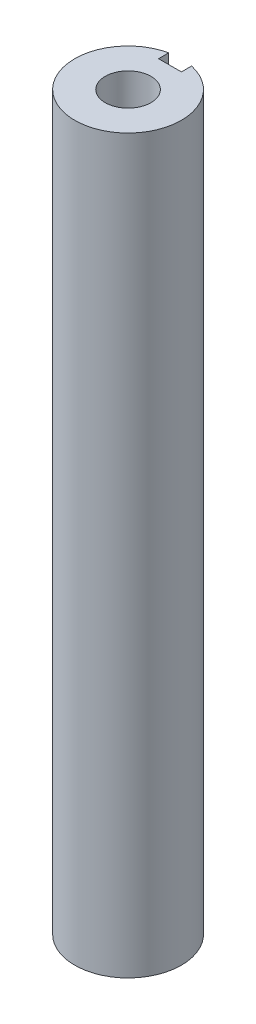
SolidWorks part; units mm, degrees
material "AISI 1045 Steel, cold drawn"
ref_plane "Front Plane" through (0, 0, 0) normal (0, 0, 1) x (1, 0, 0)
ref_plane "Top Plane" through (0, 0, 0) normal (0, 1, 0) x (1, 0, 0)
ref_plane "Right Plane" through (0, 0, 0) normal (1, 0, 0) x (0, 0, -1)
sketch "Sketch1" plane through (0, 0, 0) normal (0, 1, 0) x (1, 0, 0)
  line L0 (0, 0) -> (0, 74.8181) construction
  line L2 (-2.3813, 10.8544) -> (-2.3813, 8.7312)
  line L3 (-2.3813, 8.7312) -> (2.3813, 8.7312)
  line L4 (2.3813, 10.8544) -> (2.3813, 8.7312)
  line L5 (4.0598, 11.1125) -> (-6.0262, 11.1125) construction
  arc A1 (2.3813, 10.8544) -> (-2.3813, 10.8544) centre (0, 0) cw
  circle A2 centre (0, 0) radius 4.7625
  dimension "D1" = 6.35
  dimension "7/16" = 11.1125
  dimension "D2" = 4.7625
  dimension "D3" = 2.3813
extrude "Shaft" add sketch "Sketch1" along normal blind 152.4
sketch "Sketch3" plane through (0, 0, 0) normal (0, 0, 1) x (1, 0, 0)
  line L0 (0, 0) -> (0, 129.54)
  circle A0 centre (0, 129.54) radius 1.7859
  circle A1 centre (0, 129.54) radius 1.7859 construction
extrude "Cut-Extrude1" [suppressed] cut sketch "Sketch3" against normal through all both and the other way through all contours A0
chamfer "Chamfer1" [suppressed] distance 0.254 angle 45
